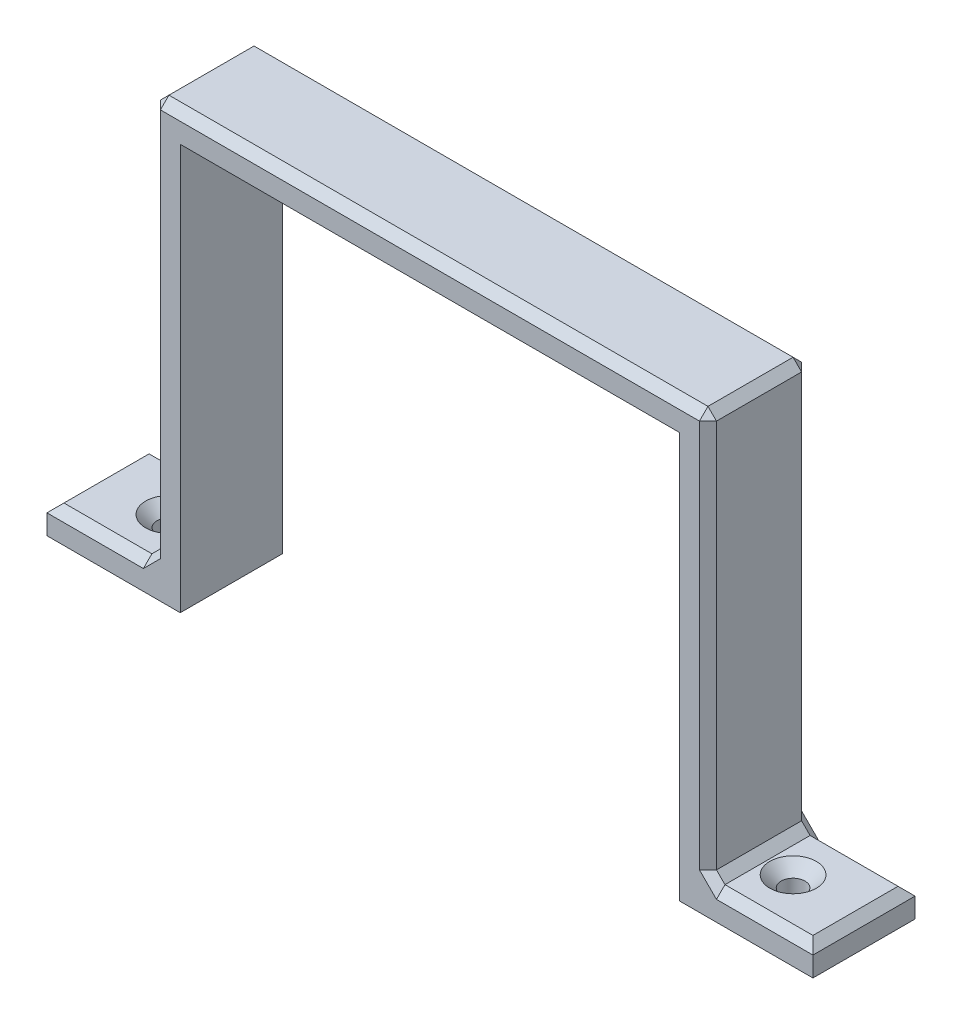
SolidWorks part; units mm, degrees
ref_plane "Front Plane" through (0, 0, 0) normal (0, 0, 1) x (1, 0, 0)
ref_plane "Top Plane" through (0, 0, 0) normal (0, 1, 0) x (1, 0, 0)
ref_plane "Right Plane" through (0, 0, 0) normal (1, 0, 0) x (0, 0, -1)
sketch "Sketch1" plane through (0, 0, 0) normal (0, 0, 1) x (1, 0, 0)
  line L0 (0, 48.7073) -> (0, -14.6895) construction
  line L1 (44, -27.85) -> (44, 43.65)
  line L2 (56.3161, -27.85) -> (55.25, -27.85) construction
  line L3 (44, 43.65) -> (-44, 43.65)
  line L4 (-49, 48.65) -> (49, 48.65)
  line L5 (49, 48.65) -> (49, -22.85)
  line L6 (49, -22.85) -> (67.5, -22.85)
  line L7 (67.5, -22.85) -> (67.5, -27.85)
  line L8 (67.5, -27.85) -> (67.5, -43.45) construction
  line L9 (67.5, -27.85) -> (44, -27.85)
  line L10 (49, -22.85) -> (49, -27.85) construction
  line L11 (0, 48.65) -> (0, 43.65) construction
  line L12 (-49, -22.85) -> (-49, -27.85) construction
  line L13 (-67.5, -27.85) -> (-44, -27.85)
  line L14 (-67.5, -22.85) -> (-67.5, -27.85)
  line L15 (-49, -22.85) -> (-67.5, -22.85)
  line L16 (-49, 48.65) -> (-49, -22.85)
  line L17 (-44, -27.85) -> (-44, 43.65)
  dimension "D1" = 71.5
  dimension "D2" = 44
  dimension "D3" = 5
  dimension "D4" = 5
  dimension "D5" = 5
extrude "Boss-Extrude1" add sketch "Sketch1" along normal mid plane 18
sketch "Sketch2" plane through (0, -27.85, 0) normal (0, -1, 0) x (1, 0, 0)
  line L0 (0, 8.47) -> (0, -7.1138) construction
  circle A0 centre (55, 0) radius 2.1
  circle A1 centre (-55, 0) radius 2.1
  dimension "D1" = 4.2
extrude "Cut-Extrude1" cut sketch "Sketch2" against normal mid plane 18
chamfer "Chamfer1" distance 2 angle 45 2 edges at (-52.9, -22.85, 0) (55, -22.85, -2.1)
chamfer "Chamfer2" distance 1.5 angle 45 16 edges at (49, 48.65, 0) (0, 48.65, 9) (-49, 48.65, 0) (0, 48.65, -9) (-49, 12.9, 9) (-49, 12.9, -9) (-49, -22.85, 0) (-58.25, -22.85, 9) (-67.5, -22.85, 0) (-58.25, -22.85, -9) (49, 12.9, 9) (49, 12.9, -9) (67.5, -22.85, 0) (58.25, -22.85, 9) (49, -22.85, 0) (58.25, -22.85, -9)
